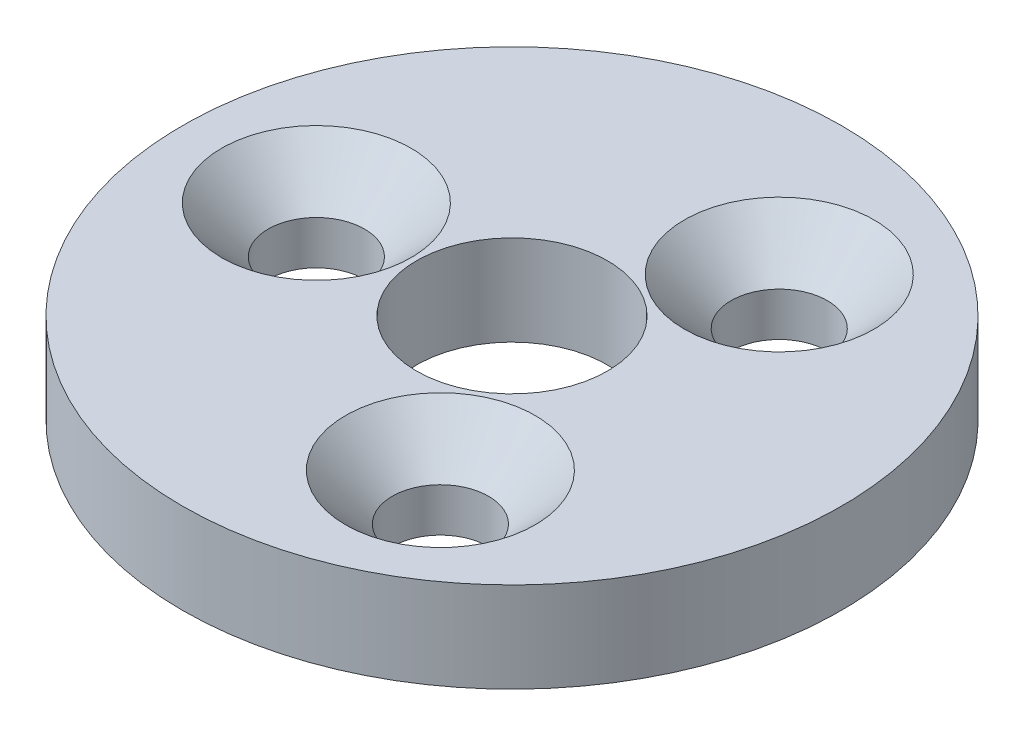
SolidWorks part; units mm, degrees
ref_plane "Front Plane" through (0, 0, 0) normal (0, 0, 1) x (1, 0, 0)
ref_plane "Top Plane" through (0, 0, 0) normal (0, 1, 0) x (1, 0, 0)
ref_plane "Right Plane" through (0, 0, 0) normal (1, 0, 0) x (0, 0, -1)
sketch "Sketch1" plane through (0, 0, 0) normal (0, 1, 0) x (1, 0, 0)
  circle A0 centre (0, 0) radius 10.95
  circle A2 centre (0, 0) radius 3.175
  dimension "D3" = 21.9
  dimension "D4" = 6.35
extrude "Boss-Extrude1" add sketch "Sketch1" along normal blind 3
sketch "Sketch5" plane through (0, 3, 0) normal (0, 1, 0) x (1, 0, 0)
  line L0 (0, 0) -> (-10.95, 0) construction
  line L1 (0, 0) -> (5.475, 9.483) construction
  line L2 (0, 0) -> (5.475, -9.483) construction
  circle A0 centre (0, 0) radius 10.95 construction
  circle A1 centre (-6.5, 0) radius 1.5
  circle A2 centre (3.25, 5.6292) radius 1.5
  circle A3 centre (3.25, -5.6292) radius 1.5
  circle A4 centre (0, 0) radius 6.5 construction
  dimension "D2" = 3
  dimension "D3" = 13
  dimension "D1" = 120
  dimension "D6" = 120
hole_wizard "CSK for M3 Countersunk Raised Head Screw1" positions "Sketch2" profile "Sketch4" countersink size "M3" standard "ISO" end condition through all
sketch "Sketch2" plane through (0, 3, 0) normal (0, 1, 0) x (1, 0, 0)
  point P12 (-6.5, 0)
  point P15 (3.25, 5.6292)
  point P18 (3.25, -5.6292)
sketch "Sketch4" plane through (-6.5, 3, 0) normal (1, 0, 0) x (0, 0, 1)
  line L0 (0, 0) -> (0, 3)
  line L1 (0, 3) -> (1.6, 3)
  line L2 (1.6, 3) -> (1.6, 1.55)
  line L3 (1.6, 1.55) -> (3.15, 0)
  line L5 (3.15, 0) -> (0, 0)
  line L6 (-1.6, 1.55) -> (-3.15, 0) construction
  line L11 (0, -6.35) -> (0, 107.95) construction
  dimension "Thru Hole Dia." = 3.2
  dimension "Thru Hole Depth" = 3
  dimension "Near C'Sink Dia." = 6.3
  dimension "Near C'Sink Angle" = 90
equation "\"D3@Sketch1\"=21.9mm"
equation "\"D4@Sketch1\"=6.35mm"
equation "\"D1@Sketch5\"=120deg"
